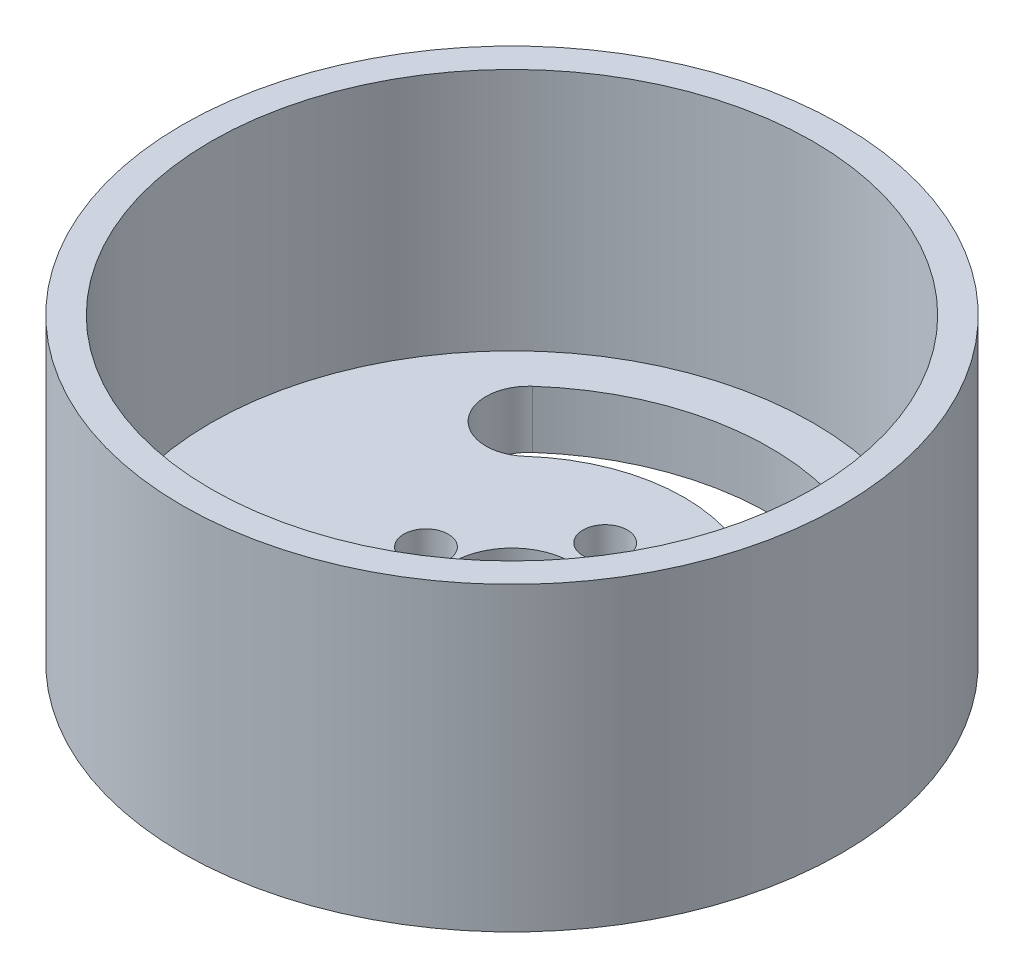
SolidWorks part; units mm, degrees
material "6061 合金"
ref_plane "前视基准面" through (0, 0, 0) normal (0, 0, 1) x (1, 0, 0)
ref_plane "上视基准面" through (0, 0, 0) normal (0, 1, 0) x (1, 0, 0)
ref_plane "右视基准面" through (0, 0, 0) normal (1, 0, 0) x (0, 0, -1)
sketch "草图1" plane through (0, 0, 0) normal (0, 1, 0) x (1, 0, 0)
  circle A0 centre (0, 0) radius 23
  circle A1 centre (0, 0) radius 21
  dimension "D1" = 42
  dimension "D2" = 46
extrude "凸台-拉伸1" add sketch "草图1" along normal blind 21
sketch "草图2" plane through (0, 0, 0) normal (0, -1, 0) x (1, 0, 0)
  line L0 (11.55, 0) -> (-11.55, 0) construction
  line L1 (0, 15) -> (0, -15) construction
  circle A0 centre (0, 0) radius 23
  arc A1 (-10, 11.1803) -> (10, 11.1803) centre (0, 0) cw construction
  arc A2 (12, 13.4164) -> (-12, 13.4164) centre (0, 0) ccw
  arc A3 (8, 8.9443) -> (-8, 8.9443) centre (0, 0) ccw
  arc A4 (8, 8.9443) -> (12, 13.4164) centre (10, 11.1803) ccw
  arc A5 (-12, 13.4164) -> (-8, 8.9443) centre (-10, 11.1803) ccw
  arc A6 (-10, -11.1803) -> (10, -11.1803) centre (0, 0) ccw construction
  arc A7 (12, -13.4164) -> (-12, -13.4164) centre (0, 0) cw
  arc A8 (8, -8.9443) -> (-8, -8.9443) centre (0, 0) cw
  arc A9 (8, -8.9443) -> (12, -13.4164) centre (10, -11.1803) cw
  arc A10 (-12, -13.4164) -> (-8, -8.9443) centre (-10, -11.1803) cw
  circle A11 centre (0, 0) radius 4.15
  circle A12 centre (6, 0) radius 1.55
  circle A13 centre (-6, 0) radius 1.55
  circle A14 centre (0, 6.5) radius 1.55
  circle A15 centre (0, -6.5) radius 1.55
  point P5 (0, 15)
  point P14 (0, -15)
  point P37 (0, -15)
  dimension "D1" = 6
  dimension "D2" = 6
  dimension "D3" = 6.5
  dimension "D4" = 6.5
  dimension "D5" = 8.3
  dimension "D6" = 3.1
  dimension "D7" = 15
  dimension "D8" = 18
  dimension "D9" = 10
extrude "凸台-拉伸2" add sketch "草图2" against normal blind 4
